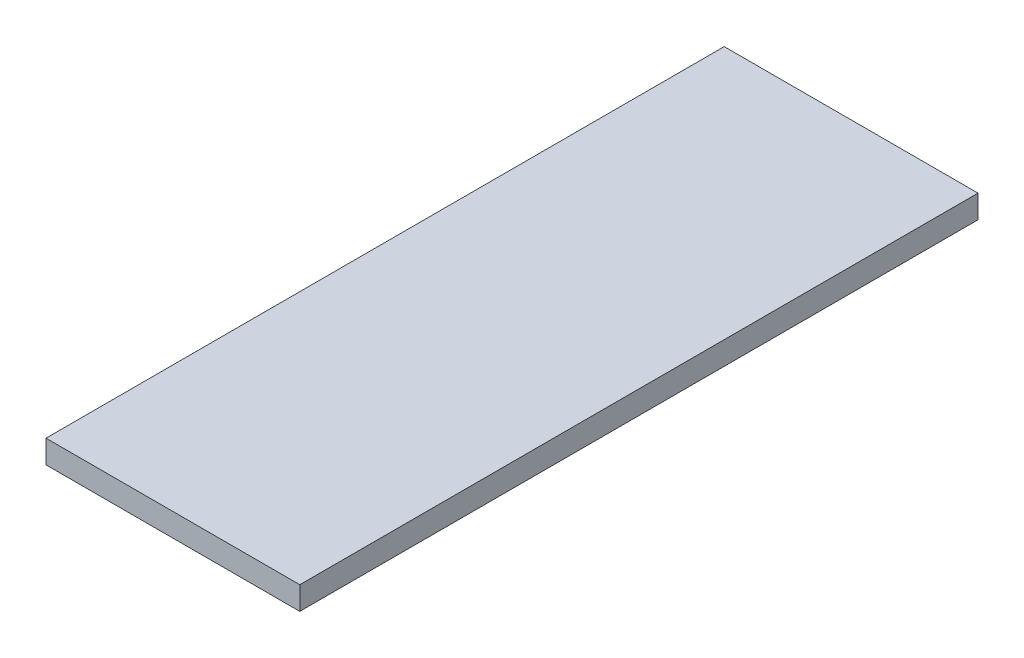
SolidWorks part; units mm, degrees
ref_plane "Front Plane" through (0, 0, 0) normal (0, 0, 1) x (1, 0, 0)
ref_plane "Top Plane" through (0, 0, 0) normal (0, 1, 0) x (1, 0, 0)
ref_plane "Right Plane" through (0, 0, 0) normal (1, 0, 0) x (0, 0, -1)
sketch "Sketch1" plane through (0, 0, 0) normal (0, 0, 1) x (1, 0, 0)
  line L0 (-528.0858, 1862.9968) -> (-737.1845, 1862.9968)
  line L1 (-737.1845, 1862.9968) -> (-737.1845, 1843.9468)
  line L2 (-528.0858, 1862.9968) -> (-528.0858, 1843.9468)
  line L6 (-528.0858, 1843.9468) -> (-737.1845, 1843.9468)
  dimension "D1" = 19.05
extrude "Boss-Extrude1" add sketch "Sketch1" along normal blind 558.8
